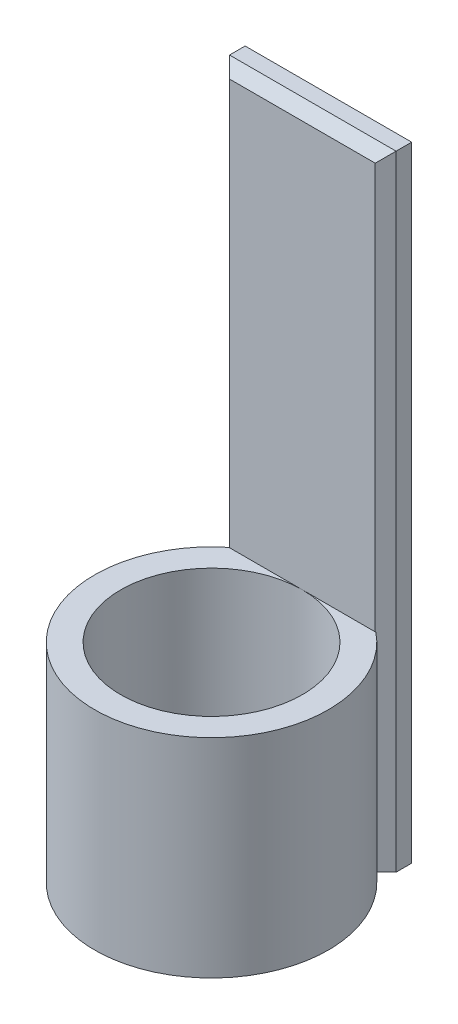
SolidWorks part; units mm, degrees
ref_plane "Front Plane" through (0, 0, 0) normal (0, 0, 1) x (1, 0, 0)
ref_plane "Top Plane" through (0, 0, 0) normal (0, 1, 0) x (1, 0, 0)
ref_plane "Right Plane" through (0, 0, 0) normal (1, 0, 0) x (0, 0, -1)
sketch "Sketch1" plane through (0, 0, 0) normal (0, 1, 0) x (1, 0, 0)
  circle A0 centre (0, 0) radius 4.3652
  circle A1 centre (0, 0) radius 5.6152
  dimension "D1" = 1.25
extrude "Boss-Extrude1" add sketch "Sketch1" along normal blind 10
ref_plane "Plane1" through (0, 0, -4.3652) normal (0, 0, 1) x (1, 0, 0)
sketch "Sketch2" plane through (0, 0, -4.3652) normal (0, 0, 1) x (1, 0, 0)
  line L0 (-5.6152, 0) -> (5.6152, 0) construction
  line L1 (4, 0) -> (-4, 0)
  line L2 (4, 0) -> (4, 30)
  line L3 (4, 30) -> (-4, 30)
  line L4 (-4, 0) -> (-4, 30)
  line L5 (4, 0) -> (-4, 30) construction
  line L6 (4, 30) -> (-4, 0) construction
  point P4 (0, 15)
  point P7 (-5.456, 0)
  point P8 (0, 0)
  dimension "D1" = 8
  dimension "D2" = 30
extrude "Boss-Extrude2" add sketch "Sketch2" against normal blind 1.25
fillet "Fillet1" radius 0.2 1 edges at (0, 0, 4.3652)
chamfer "Chamfer1" distance 0.5 angle 45 3 edges at (-4, 15, -4.3652) (0, 30, -4.3652) (4, 15, -4.3652)
